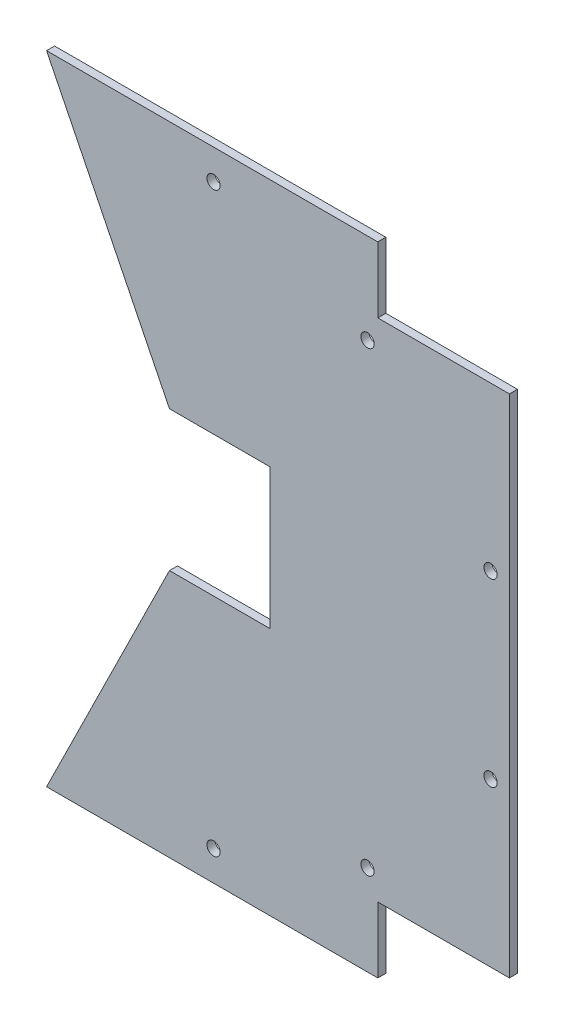
SolidWorks part; units mm, degrees
ref_plane "Front Plane" through (0, 0, 0) normal (0, 0, 1) x (1, 0, 0)
ref_plane "Top Plane" through (0, 0, 0) normal (0, 1, 0) x (1, 0, 0)
ref_plane "Right Plane" through (0, 0, 0) normal (1, 0, 0) x (0, 0, -1)
sketch "Sketch2" plane through (0, 0, 0) normal (0, 0, 1) x (-1, 0, 0)
  line L11 (-2.9301, 168.7083) -> (38.7094, 168.7083)
  line L12 (-2.9301, 8.6883) -> (38.7094, 8.6883)
  line L13 (38.7094, -12.1397) -> (38.7094, 8.6883)
  line L14 (143.4971, -12.1397) -> (38.7094, -12.1397)
  line L15 (38.7094, 189.5363) -> (38.7094, 168.7083)
  line L16 (143.4971, 189.5363) -> (38.7094, 189.5363)
  line L17 (104.6174, 110.8598) -> (143.4971, 189.5363)
  line L18 (104.6174, 66.5368) -> (143.4971, -12.1397)
  line L19 (104.6174, 66.5368) -> (72.8674, 66.5368)
  line L20 (72.8674, 66.5368) -> (72.8674, 110.8598)
  line L21 (104.6174, 110.8598) -> (72.8674, 110.8598)
  line L22 (-2.9301, 168.7083) -> (-2.9301, 8.6883)
  line L23 (41.9566, 19.6103) -> (41.9566, 13.2603) construction
  circle A0 centre (41.9566, 160.9613) radius 2.0955
  circle A1 centre (90.6739, 180.0113) radius 2.0955
  circle A2 centre (90.6739, -2.6147) radius 2.0955
  circle A3 centre (3.0351, 117.2098) radius 2.0955
  circle A4 centre (3.0351, 60.1868) radius 2.0955
  circle A5 centre (41.9566, 16.4353) radius 2.0955
  point P35 (41.9566, 14.7329)
  point P36 (41.9566, 16.4353)
  dimension "D1" = 4.191
  dimension "D2" = 4.191
  dimension "D3" = 4.191
  dimension "D4" = 4.191
  dimension "D5" = 4.191
  dimension "D6" = 4.191
extrude "Boss-Extrude1" add sketch "Sketch2" along normal blind 2.54
